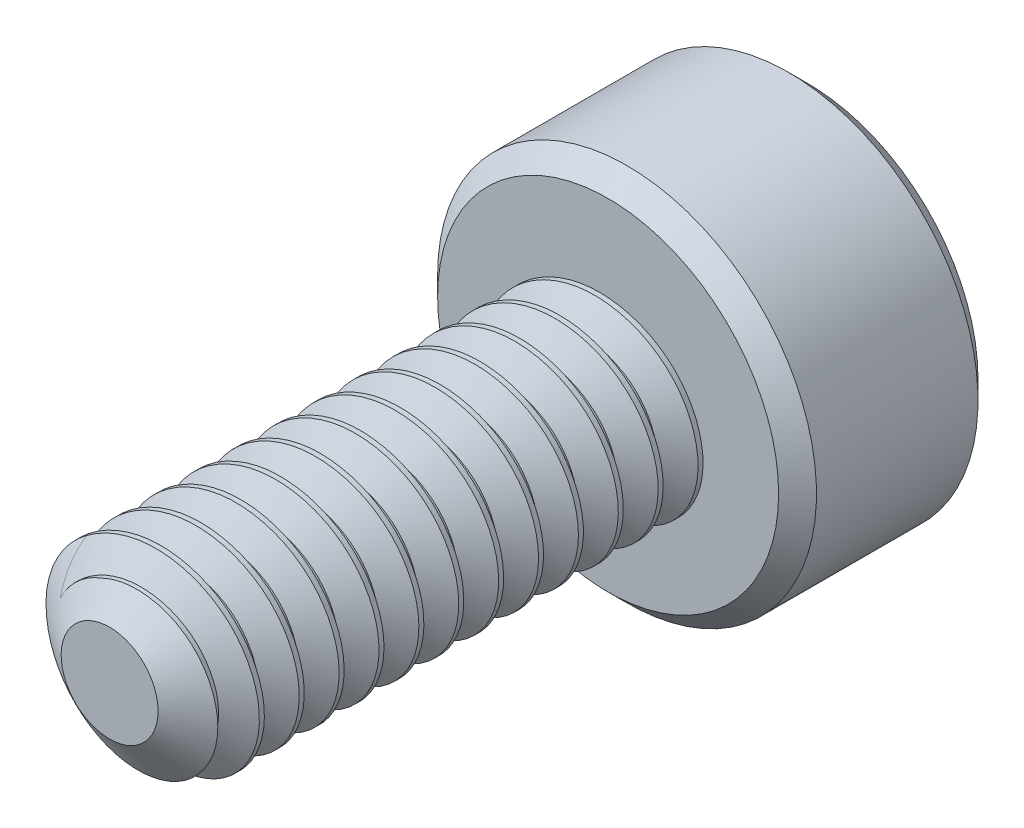
SolidWorks part; units mm, degrees
other "DetailItem1"
ref_plane "Front Plane" through (0, 0, 0) normal (0, 0, 1) x (1, 0, 0)
ref_plane "Top Plane" through (0, 0, 0) normal (0, 1, 0) x (1, 0, 0)
ref_plane "Right Plane" through (0, 0, 0) normal (1, 0, 0) x (0, 0, -1)
sketch "Sketch1" plane through (0, 0, 0) normal (0, 0, 1) x (1, 0, 0)
  circle A0 centre (0, 0) radius 1
  dimension "OD" = 2
extrude "Extrude1" add sketch "Sketch1" against normal blind 5
sketch "Sketch2" plane through (0, 0, 0) normal (0, 0, 1) x (1, 0, 0)
  circle A0 centre (0, 0) radius 1 construction
  circle A1 centre (0, 0) radius 1
curve "Helix/Spiral1" pitch 0.4 height 5.4 radius 1 centre (0, 0, 0) axis (0, 0, -1) start towards (0, 1, 0) parameters "pitch"=0.4
sketch "Sketch3" plane through (0, 0, 0) normal (1, 0, 0) x (0, 0, -1)
  line L0 (-0.35, 1) -> (-0.2, 0.7402)
  line L1 (-0.2, 0.7402) -> (-0.15, 0.7402)
  line L2 (-0.15, 0.7402) -> (0, 1)
  line L3 (-0.35, 1) -> (0, 1)
  line L4 (-0.175, 1) -> (-0.175, 0.7402) construction
  line L5 (-0.275, 0.8701) -> (-0.075, 0.8701) construction
  line L6 (0, 1) -> (0, -1) construction
  dimension "D1" = 0.05
  dimension "D2" = 0.2
  dimension "D3" = 60
sweep "Cut-Sweep1" cut profiles "Sketch3" path "Helix/Spiral1"
sketch "Sketch4" plane through (0, 0, 0) normal (1, 0, 0) x (0, 0, -1)
  line L0 (0.3598, 1) -> (0, 0.4862)
  line L1 (0, 0.4862) -> (0, 1)
  line L2 (0.3598, 1) -> (0, 1)
  line L3 (-0.35, 1) -> (0, 1) construction
  line L4 (0, 0) -> (7.0209, 0) construction
  dimension "D1" = 55
  dimension "D2" = 0.254
revolve "Cut-Revolve1" cut sketch "Sketch4" angle 360 about L4
sketch "Sketch6" plane through (0, 0, -5) normal (0, 0, -1) x (-1, 0, 0)
  circle A0 centre (0, 0) radius 1.9
  dimension "head dia" = 3.8
extrude "Extrude2" add sketch "Sketch6" along normal blind 2
sketch "Sketch7" plane through (0, 0, -7) normal (0, 0, -1) x (-1, 0, 0)
  line L1 (0, 0.866) -> (-0.75, 0.433)
  line L2 (-0.75, 0.433) -> (-0.75, -0.433)
  line L3 (-0.75, -0.433) -> (0, -0.866)
  line L4 (0, -0.866) -> (0.75, -0.433)
  line L5 (0.75, -0.433) -> (0.75, 0.433)
  line L6 (0.75, 0.433) -> (0, 0.866)
  circle A0 centre (0, 0) radius 0.75 construction
  dimension "hex dia" = 1.5
extrude "Cut-Extrude1" cut sketch "Sketch7" against normal blind 1.125
sketch "Sketch8" plane through (0, 0, -7) normal (0, 0, -1) x (-1, 0, 0)
  circle A0 centre (0, 0) radius 0.866
extrude "Cut-Extrude2" cut sketch "Sketch8" against normal through all draft 45
chamfer "Chamfer1" distance 0.19 angle 45 2 edges at (-1.9, 0, -7) (-1.9, 0, -5)
sketch "Sketch10" plane through (0, 0, -5) normal (0, 0, 1) x (1, 0, 0)
  circle A1 centre (0, 0) radius 1
  circle A2 centre (0, 0) radius 1
  dimension "D1" = 0
ref_plane "Plane1" through (0, 0, 0) normal (0, 0, 1) x (1, 0, 0)
extrude "partial thread" [suppressed] add sketch "Sketch10" along normal up to surface (2 mm away) separate body up to plane "Plane1"
chamfer "Chamfer2" [suppressed] distance 0.04 angle 45
combine bodies "Combine1" [suppressed] operation type add bodies to combine 107 108
sketch "Sketch9" plane through (0, 0, 0) normal (1, 0, 0) x (0, 0, -1)
  line L0 (0, 1) -> (0, -1) construction
  line L1 (1, 1) -> (1, -1) construction
  dimension "D1" = 1
equation "\"D3@Helix/Spiral1\" = \"screw length@Extrude1\"+\"pitch@Helix/Spiral1\""
equation "\"D1@Sketch3\" = \"pitch@Helix/Spiral1\"*.125"
equation "\"D2@Sketch3\" = \"pitch@Helix/Spiral1\"*.5"
equation "\"D1@Cut-Extrude1\" = \"hex dia@Sketch7\"*.75"
equation "\"D1@Chamfer1\" = \"head dia@Sketch6\"*.05"
equation "\"D1@Sketch9\" = \"pitch@Helix/Spiral1\"*2.5"
equation "\"D1@Chamfer2\"=\"OD@Sketch1\"*.02"
